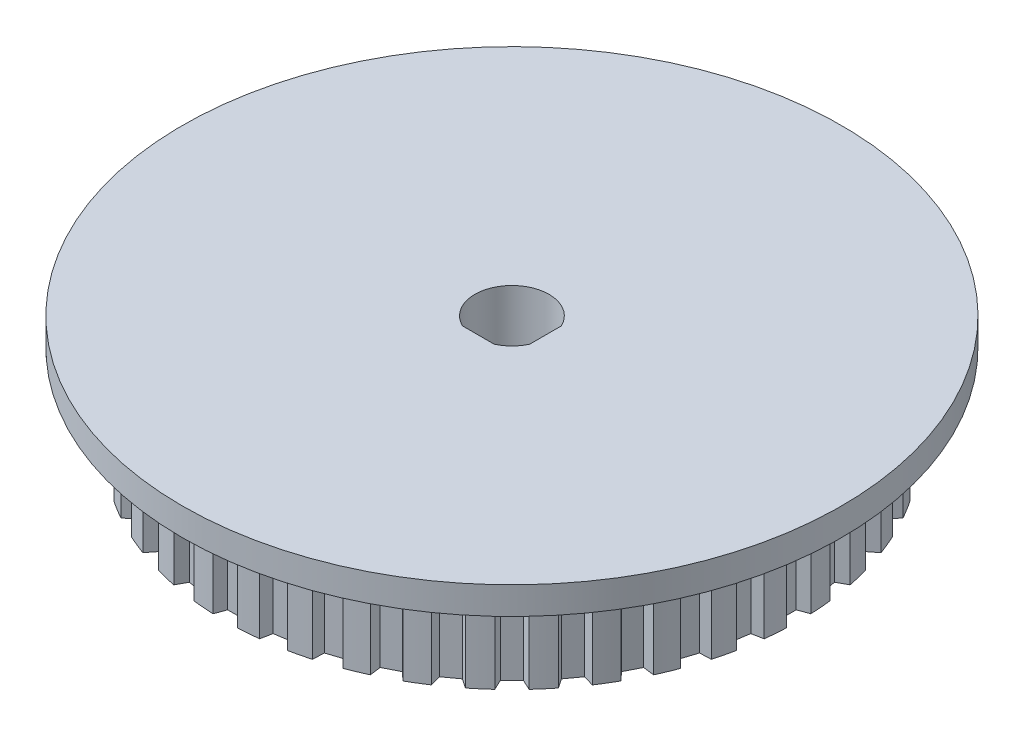
SolidWorks part; units mm, degrees
ref_plane "Спереди" through (0, 0, 0) normal (0, 0, 1) x (1, 0, 0)
ref_plane "Сверху" through (0, 0, 0) normal (0, 1, 0) x (1, 0, 0)
ref_plane "Справа" through (0, 0, 0) normal (1, 0, 0) x (0, 0, -1)
sketch "Эскиз1" plane through (0, 0, 0) normal (0, 1, 0) x (1, 0, 0)
  line L0 (0, 32.35) -> (0, 0) construction
  line L1 (-0.9, 30.15) -> (0.9, 30.15)
  line L2 (-0.9, 30.15) -> (-1.3265, 31.3219)
  line L3 (0.9, 30.15) -> (1.3265, 31.3219)
  line L4 (3.8276, 29.9196) -> (3.5896, 31.1438)
  line L5 (3.8276, 29.9196) -> (5.6054, 29.638)
  line L6 (5.6054, 29.638) -> (6.21, 30.7288)
  line L7 (8.4609, 28.9525) -> (8.4174, 30.1988)
  line L8 (8.4609, 28.9525) -> (10.1728, 28.3962)
  line L9 (10.1728, 28.3962) -> (10.9406, 29.379)
  line L10 (12.8859, 27.2724) -> (13.0379, 28.5103)
  line L11 (12.8859, 27.2724) -> (14.4897, 26.4553)
  line L12 (14.4897, 26.4553) -> (15.4018, 27.3058)
  line L13 (16.9936, 24.9209) -> (17.3374, 26.1197)
  line L14 (16.9936, 24.9209) -> (18.4498, 23.8629)
  line L15 (18.4498, 23.8629) -> (19.4838, 24.5602)
  line L16 (20.6829, 21.9557) -> (21.2099, 23.086)
  line L17 (20.6829, 21.9557) -> (21.9557, 20.6829)
  line L18 (21.9557, 20.6829) -> (23.086, 21.2099)
  line L19 (23.8629, 18.4498) -> (24.5602, 19.4838)
  line L20 (23.8629, 18.4498) -> (24.9209, 16.9936)
  line L21 (24.9209, 16.9936) -> (26.1197, 17.3374)
  line L22 (26.4553, 14.4897) -> (27.3058, 15.4018)
  line L23 (26.4553, 14.4897) -> (27.2724, 12.8859)
  line L24 (27.2724, 12.8859) -> (28.5103, 13.0379)
  line L25 (28.3962, 10.1728) -> (29.379, 10.9406)
  line L26 (28.3962, 10.1728) -> (28.9525, 8.4609)
  line L27 (28.9525, 8.4609) -> (30.1988, 8.4174)
  line L28 (29.638, 5.6054) -> (30.7288, 6.21)
  line L29 (29.638, 5.6054) -> (29.9196, 3.8276)
  line L30 (29.9196, 3.8276) -> (31.1438, 3.5896)
  line L31 (30.15, 0.9) -> (31.3219, 1.3265)
  line L32 (30.15, 0.9) -> (30.15, -0.9)
  line L33 (30.15, -0.9) -> (31.3219, -1.3265)
  line L34 (29.9196, -3.8276) -> (31.1438, -3.5896)
  line L35 (29.9196, -3.8276) -> (29.638, -5.6054)
  line L36 (29.638, -5.6054) -> (30.7288, -6.21)
  line L37 (28.9525, -8.4609) -> (30.1988, -8.4174)
  line L38 (28.9525, -8.4609) -> (28.3962, -10.1728)
  line L39 (28.3962, -10.1728) -> (29.379, -10.9406)
  line L40 (27.2724, -12.8859) -> (28.5103, -13.0379)
  line L41 (27.2724, -12.8859) -> (26.4553, -14.4897)
  line L42 (26.4553, -14.4897) -> (27.3058, -15.4018)
  line L43 (24.9209, -16.9936) -> (26.1197, -17.3374)
  line L44 (24.9209, -16.9936) -> (23.8629, -18.4498)
  line L45 (23.8629, -18.4498) -> (24.5602, -19.4838)
  line L46 (21.9557, -20.6829) -> (23.086, -21.2099)
  line L47 (21.9557, -20.6829) -> (20.6829, -21.9557)
  line L48 (20.6829, -21.9557) -> (21.2099, -23.086)
  line L49 (18.4498, -23.8629) -> (19.4838, -24.5602)
  line L50 (18.4498, -23.8629) -> (16.9936, -24.9209)
  line L51 (16.9936, -24.9209) -> (17.3374, -26.1197)
  line L52 (14.4897, -26.4553) -> (15.4018, -27.3058)
  line L53 (14.4897, -26.4553) -> (12.8859, -27.2724)
  line L54 (12.8859, -27.2724) -> (13.0379, -28.5103)
  line L55 (10.1728, -28.3962) -> (10.9406, -29.379)
  line L56 (10.1728, -28.3962) -> (8.4609, -28.9525)
  line L57 (8.4609, -28.9525) -> (8.4174, -30.1988)
  line L58 (5.6054, -29.638) -> (6.21, -30.7288)
  line L59 (5.6054, -29.638) -> (3.8276, -29.9196)
  line L60 (3.8276, -29.9196) -> (3.5896, -31.1438)
  line L61 (0.9, -30.15) -> (1.3265, -31.3219)
  line L62 (0.9, -30.15) -> (-0.9, -30.15)
  line L63 (-0.9, -30.15) -> (-1.3265, -31.3219)
  line L64 (-3.8276, -29.9196) -> (-3.5896, -31.1438)
  line L65 (-3.8276, -29.9196) -> (-5.6054, -29.638)
  line L66 (-5.6054, -29.638) -> (-6.21, -30.7288)
  line L67 (-8.4609, -28.9525) -> (-8.4174, -30.1988)
  line L68 (-8.4609, -28.9525) -> (-10.1728, -28.3962)
  line L69 (-10.1728, -28.3962) -> (-10.9406, -29.379)
  line L70 (-12.8859, -27.2724) -> (-13.0379, -28.5103)
  line L71 (-12.8859, -27.2724) -> (-14.4897, -26.4553)
  line L72 (-14.4897, -26.4553) -> (-15.4018, -27.3058)
  line L73 (-16.9936, -24.9209) -> (-17.3374, -26.1197)
  line L74 (-16.9936, -24.9209) -> (-18.4498, -23.8629)
  line L75 (-18.4498, -23.8629) -> (-19.4838, -24.5602)
  line L76 (-20.6829, -21.9557) -> (-21.2099, -23.086)
  line L77 (-20.6829, -21.9557) -> (-21.9557, -20.6829)
  line L78 (-21.9557, -20.6829) -> (-23.086, -21.2099)
  line L79 (-23.8629, -18.4498) -> (-24.5602, -19.4838)
  line L80 (-23.8629, -18.4498) -> (-24.9209, -16.9936)
  line L81 (-24.9209, -16.9936) -> (-26.1197, -17.3374)
  line L82 (-26.4553, -14.4897) -> (-27.3058, -15.4018)
  line L83 (-26.4553, -14.4897) -> (-27.2724, -12.8859)
  line L84 (-27.2724, -12.8859) -> (-28.5103, -13.0379)
  line L85 (-28.3962, -10.1728) -> (-29.379, -10.9406)
  line L86 (-28.3962, -10.1728) -> (-28.9525, -8.4609)
  line L87 (-28.9525, -8.4609) -> (-30.1988, -8.4174)
  line L88 (-29.638, -5.6054) -> (-30.7288, -6.21)
  line L89 (-29.638, -5.6054) -> (-29.9196, -3.8276)
  line L90 (-29.9196, -3.8276) -> (-31.1438, -3.5896)
  line L91 (-30.15, -0.9) -> (-31.3219, -1.3265)
  line L92 (-30.15, -0.9) -> (-30.15, 0.9)
  line L93 (-30.15, 0.9) -> (-31.3219, 1.3265)
  line L94 (-29.9196, 3.8276) -> (-31.1438, 3.5896)
  line L95 (-29.9196, 3.8276) -> (-29.638, 5.6054)
  line L96 (-29.638, 5.6054) -> (-30.7288, 6.21)
  line L97 (-28.9525, 8.4609) -> (-30.1988, 8.4174)
  line L98 (-28.9525, 8.4609) -> (-28.3962, 10.1728)
  line L99 (-28.3962, 10.1728) -> (-29.379, 10.9406)
  line L100 (-27.2724, 12.8859) -> (-28.5103, 13.0379)
  line L101 (-27.2724, 12.8859) -> (-26.4553, 14.4897)
  line L102 (-26.4553, 14.4897) -> (-27.3058, 15.4018)
  line L103 (-24.9209, 16.9936) -> (-26.1197, 17.3374)
  line L104 (-24.9209, 16.9936) -> (-23.8629, 18.4498)
  line L105 (-23.8629, 18.4498) -> (-24.5602, 19.4838)
  line L106 (-21.9557, 20.6829) -> (-23.086, 21.2099)
  line L107 (-21.9557, 20.6829) -> (-20.6829, 21.9557)
  line L108 (-20.6829, 21.9557) -> (-21.2099, 23.086)
  line L109 (-18.4498, 23.8629) -> (-19.4838, 24.5602)
  line L110 (-18.4498, 23.8629) -> (-16.9936, 24.9209)
  line L111 (-16.9936, 24.9209) -> (-17.3374, 26.1197)
  line L112 (-14.4897, 26.4553) -> (-15.4018, 27.3058)
  line L113 (-14.4897, 26.4553) -> (-12.8859, 27.2724)
  line L114 (-12.8859, 27.2724) -> (-13.0379, 28.5103)
  line L115 (-10.1728, 28.3962) -> (-10.9406, 29.379)
  line L116 (-10.1728, 28.3962) -> (-8.4609, 28.9525)
  line L117 (-8.4609, 28.9525) -> (-8.4174, 30.1988)
  line L118 (-5.6054, 29.638) -> (-6.21, 30.7288)
  line L119 (-5.6054, 29.638) -> (-3.8276, 29.9196)
  line L120 (-3.8276, 29.9196) -> (-3.5896, 31.1438)
  circle A0 centre (0, 0) radius 30.15 construction
  circle A1 centre (0, 0) radius 32.35 construction
  circle A2 centre (0, 0) radius 31.85 construction
  circle A3 centre (0, 0) radius 31.35 construction
  arc A4 (-3.5896, 31.1438) -> (-1.3265, 31.3219) centre (0, 0) cw
  arc A5 (1.3265, 31.3219) -> (3.5896, 31.1438) centre (0, 0) cw
  arc A6 (6.21, 30.7288) -> (8.4174, 30.1988) centre (0, 0) cw
  arc A7 (10.9406, 29.379) -> (13.0379, 28.5103) centre (0, 0) cw
  arc A8 (15.4018, 27.3058) -> (17.3374, 26.1197) centre (0, 0) cw
  arc A9 (19.4838, 24.5602) -> (21.2099, 23.086) centre (0, 0) cw
  arc A10 (23.086, 21.2099) -> (24.5602, 19.4838) centre (0, 0) cw
  arc A11 (26.1197, 17.3374) -> (27.3058, 15.4018) centre (0, 0) cw
  arc A12 (28.5103, 13.0379) -> (29.379, 10.9406) centre (0, 0) cw
  arc A13 (30.1988, 8.4174) -> (30.7288, 6.21) centre (0, 0) cw
  arc A14 (31.1438, 3.5896) -> (31.3219, 1.3265) centre (0, 0) cw
  arc A15 (31.3219, -1.3265) -> (31.1438, -3.5896) centre (0, 0) cw
  arc A16 (30.7288, -6.21) -> (30.1988, -8.4174) centre (0, 0) cw
  arc A17 (29.379, -10.9406) -> (28.5103, -13.0379) centre (0, 0) cw
  arc A18 (27.3058, -15.4018) -> (26.1197, -17.3374) centre (0, 0) cw
  arc A19 (24.5602, -19.4838) -> (23.086, -21.2099) centre (0, 0) cw
  arc A20 (21.2099, -23.086) -> (19.4838, -24.5602) centre (0, 0) cw
  arc A21 (17.3374, -26.1197) -> (15.4018, -27.3058) centre (0, 0) cw
  arc A22 (13.0379, -28.5103) -> (10.9406, -29.379) centre (0, 0) cw
  arc A23 (8.4174, -30.1988) -> (6.21, -30.7288) centre (0, 0) cw
  arc A24 (3.5896, -31.1438) -> (1.3265, -31.3219) centre (0, 0) cw
  arc A25 (-1.3265, -31.3219) -> (-3.5896, -31.1438) centre (0, 0) cw
  arc A26 (-6.21, -30.7288) -> (-8.4174, -30.1988) centre (0, 0) cw
  arc A27 (-10.9406, -29.379) -> (-13.0379, -28.5103) centre (0, 0) cw
  arc A28 (-15.4018, -27.3058) -> (-17.3374, -26.1197) centre (0, 0) cw
  arc A29 (-19.4838, -24.5602) -> (-21.2099, -23.086) centre (0, 0) cw
  arc A30 (-23.086, -21.2099) -> (-24.5602, -19.4838) centre (0, 0) cw
  arc A31 (-26.1197, -17.3374) -> (-27.3058, -15.4018) centre (0, 0) cw
  arc A32 (-28.5103, -13.0379) -> (-29.379, -10.9406) centre (0, 0) cw
  arc A33 (-30.1988, -8.4174) -> (-30.7288, -6.21) centre (0, 0) cw
  arc A34 (-31.1438, -3.5896) -> (-31.3219, -1.3265) centre (0, 0) cw
  arc A35 (-31.3219, 1.3265) -> (-31.1438, 3.5896) centre (0, 0) cw
  arc A36 (-30.7288, 6.21) -> (-30.1988, 8.4174) centre (0, 0) cw
  arc A37 (-29.379, 10.9406) -> (-28.5103, 13.0379) centre (0, 0) cw
  arc A38 (-27.3058, 15.4018) -> (-26.1197, 17.3374) centre (0, 0) cw
  arc A39 (-24.5602, 19.4838) -> (-23.086, 21.2099) centre (0, 0) cw
  arc A40 (-21.2099, 23.086) -> (-19.4838, 24.5602) centre (0, 0) cw
  arc A41 (-17.3374, 26.1197) -> (-15.4018, 27.3058) centre (0, 0) cw
  arc A42 (-13.0379, 28.5103) -> (-10.9406, 29.379) centre (0, 0) cw
  arc A43 (-8.4174, 30.1988) -> (-6.21, 30.7288) centre (0, 0) cw
  point P6 (0, 30.15)
  dimension "D1" = 63.7
  dimension "D2" = 64.7
  dimension "D3" = 60.3
  dimension "D4" = 62.7
  dimension "D5" = 1.8
  dimension "D6" = 20
  dimension "D7" = 20
extrude "Вытянуть1" add sketch "Эскиз1" along normal blind 10.2
sketch "Эскиз2" plane through (0, 10.2, 0) normal (0, 1, 0) x (1, 0, 0)
  circle A0 centre (0, 0) radius 36
  dimension "D1" = 72
extrude "Вытянуть2" add sketch "Эскиз2" along normal blind 3
sketch "Эскиз5" plane through (0, 13.2, 0) normal (0, 1, 0) x (1, 0, 0)
  line L0 (3.6643, 1.725) -> (3.6643, -1.725)
  line L1 (1.725, -3.6643) -> (-1.725, -3.6643)
  circle A0 centre (0, 0) radius 4.05 construction
  arc A1 (3.6643, 1.725) -> (-1.725, -3.6643) centre (0, 0) ccw
  arc A2 (1.725, -3.6643) -> (3.6643, -1.725) centre (0, 0) ccw
  dimension "D1" = 8.1
  dimension "D2" = 3.45
extrude "Вытянуть5" cut sketch "Эскиз5" against normal blind 10
sketch "Эскиз6" plane through (0, 0, 0) normal (0, -1, 0) x (1, 0, 0)
  circle A0 centre (0, 0) radius 7.5
  circle A1 centre (0, 0) radius 25
  dimension "D1" = 50
  dimension "D2" = 15
extrude "Вытянуть3" cut sketch "Эскиз6" against normal blind 10
sketch "Эскиз7" plane through (0, 0, 0) normal (0, -1, 0) x (1, 0, 0)
  circle A0 centre (0, 0) radius 4.05
  dimension "D1" = 8.1
extrude "Вытянуть4" cut sketch "Эскиз7" against normal blind 3.2
sketch "Эскиз8" plane through (0, 0, 0) normal (0, -1, 0) x (1, 0, 0)
  circle A0 centre (0, 0) radius 7.5
  circle A1 centre (0, 0) radius 4.05
  circle A2 centre (0, 0) radius 7.5 construction
  circle A3 centre (0, 0) radius 4.05 construction
extrude "Вытянуть6" add sketch "Эскиз8" along normal blind 3
